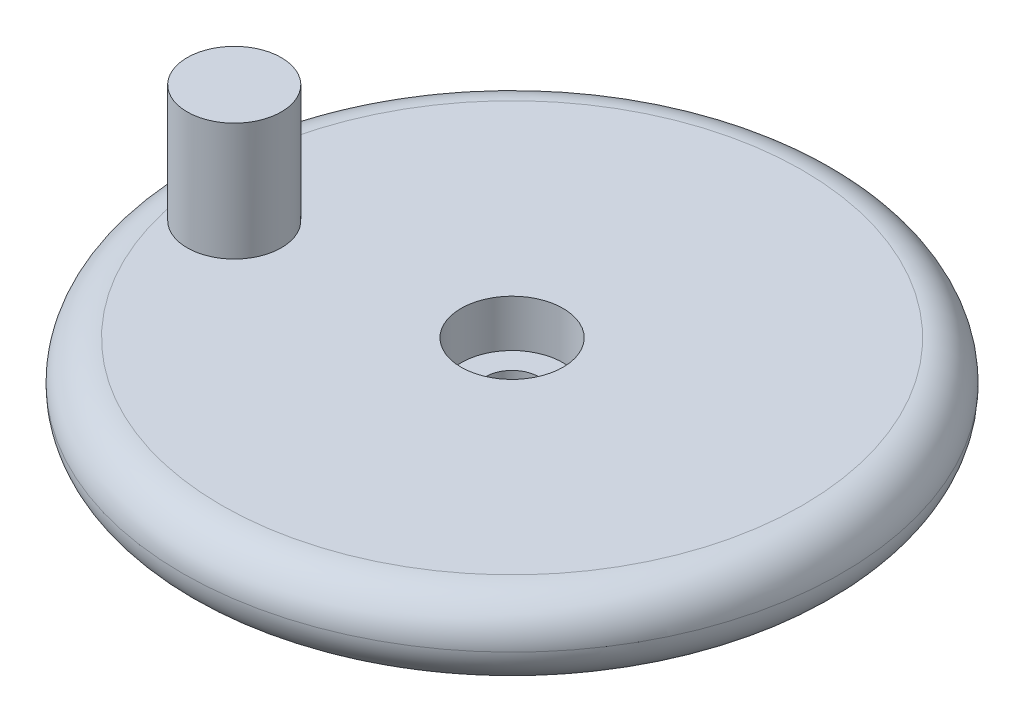
SolidWorks part; units mm, degrees
ref_plane "Front Plane" through (0, 0, 0) normal (0, 0, 1) x (1, 0, 0)
ref_plane "Top Plane" through (0, 0, 0) normal (0, 1, 0) x (1, 0, 0)
ref_plane "Right Plane" through (0, 0, 0) normal (1, 0, 0) x (0, 0, -1)
sketch "Sketch1" plane through (0, 0, 0) normal (0, 1, 0) x (1, 0, 0)
  circle A0 centre (0, 0) radius 21
  dimension "D1" = 42
extrude "Boss-Extrude1" add sketch "Sketch1" along normal blind 5
fillet "Fillet1" radius 2.5 2 edges at (0, 0, 21) (0, 5, 21)
sketch "Sketch2" plane through (0, 5, 0) normal (0, 1, 0) x (1, 0, 0)
  circle A0 centre (-15.315, -2.3879) radius 3
  circle A1 centre (0, 0) radius 18.5 construction
  dimension "D1" = 6
extrude "Boss-Extrude2" add sketch "Sketch2" along normal blind 7.5
hole_wizard "CBORE for M3 SHCS1" positions "Sketch7" profile "Sketch8" counterbore size "M3" standard "ANSI Metric" end condition through all
sketch "Sketch7" plane through (0, 5, 0) normal (0, 1, 0) x (1, 0, 0)
  point P0 (0, 0)
sketch "Sketch8" plane through (0, 5, 0) normal (1, 0, 0) x (0, 0, 1)
  line L0 (0, 0) -> (0, 5)
  line L1 (0, 5) -> (1.7, 5)
  line L3 (1.7, 5) -> (1.7, 3)
  line L4 (1.7, 3) -> (3.25, 3)
  line L5 (3.25, 3) -> (3.25, 0)
  line L7 (3.25, 0) -> (0, 0)
  line L11 (0, -6.35) -> (0, 107.95) construction
  dimension "Thru Hole Dia." = 3.4
  dimension "Thru Hole Depth" = 5
  dimension "C'Bore Dia." = 6.5
  dimension "C'Bore Depth" = 3
